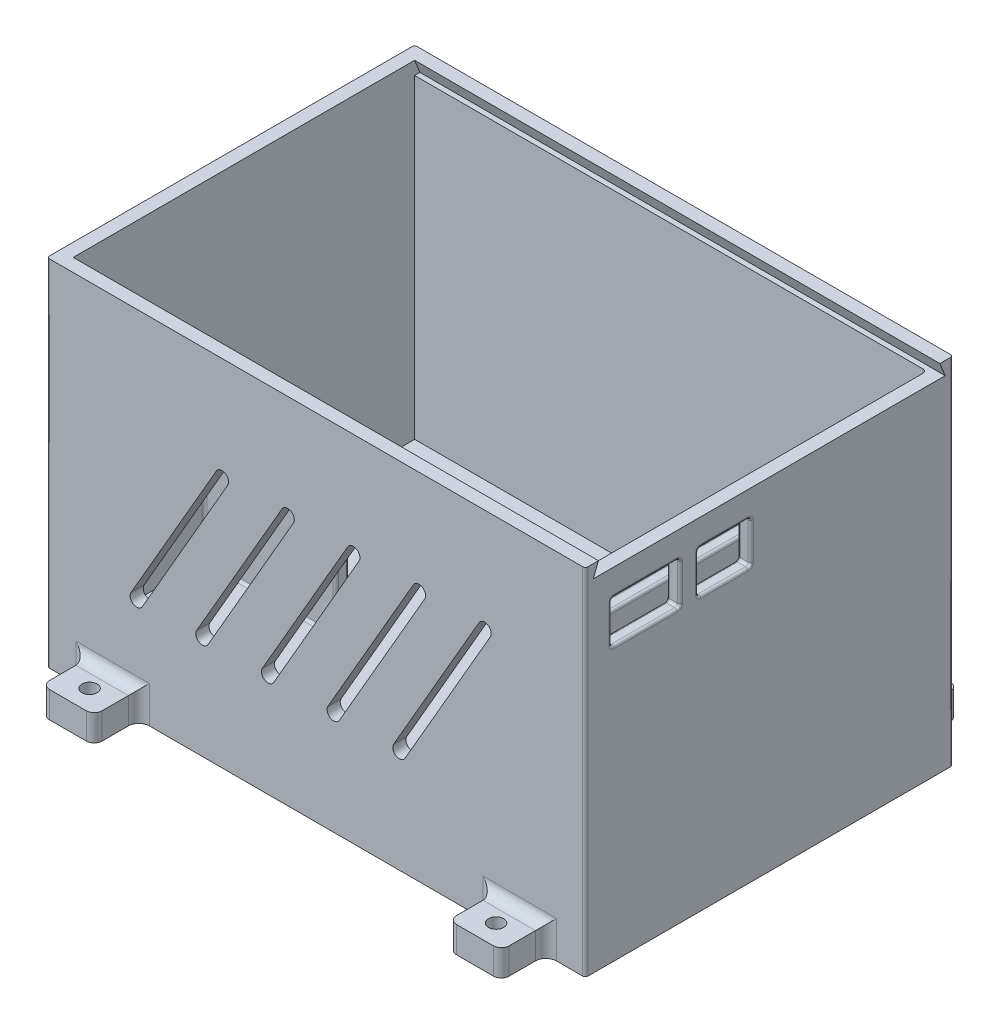
SolidWorks part; units mm, degrees
ref_plane "Front Plane" through (0, 0, 0) normal (0, 0, 1) x (1, 0, 0)
ref_plane "Top Plane" through (0, 0, 0) normal (0, 1, 0) x (1, 0, 0)
ref_plane "Right Plane" through (0, 0, 0) normal (1, 0, 0) x (0, 0, -1)
sketch "Sketch1" plane through (0, 0, 0) normal (0, 1, 0) x (1, 0, 0)
  line L1 (-90.8013, 98.9232) -> (114.1987, 98.9232)
  line L2 (-90.8013, 98.9232) -> (-90.8013, -41.0768)
  line L3 (-90.8013, -41.0768) -> (114.1987, -41.0768)
  line L4 (114.1987, 98.9232) -> (114.1987, -41.0768)
  dimension "D1" = 205
  dimension "D2" = 140
extrude "Boss-Extrude1" add sketch "Sketch1" along normal blind 130
sketch "Sketch2" plane through (0, 130, 0) normal (0, 1, 0) x (1, 0, 0)
  line L0 (114.1987, -41.0768) -> (114.1987, 98.9232) construction
  line L1 (-85.8013, 93.9232) -> (109.1987, 93.9232)
  line L2 (-85.8013, 93.9232) -> (-85.8013, -36.0768)
  line L3 (-85.8013, -36.0768) -> (109.1987, -36.0768)
  line L4 (109.1987, 93.9232) -> (109.1987, -36.0768)
  line L5 (-90.8013, 98.9232) -> (-90.8013, -41.0768) construction
  line L6 (114.1987, 98.9232) -> (-90.8013, 98.9232) construction
  line L7 (-90.8013, -41.0768) -> (114.1987, -41.0768) construction
  dimension "D2" = 5
  dimension "D3" = 5
  dimension "D1" = 5
  dimension "D4" = 5
extrude "Cut-Extrude1" cut sketch "Sketch2" against normal blind 120
sketch "Sketch3" plane through (0, 10, 0) normal (0, 1, 0) x (1, 0, 0)
  line L0 (59.1987, 93.9232) -> (59.1987, 18.9232)
  line L1 (109.1987, 93.9232) -> (-85.8013, 93.9232) construction
  line L2 (59.1987, 18.9232) -> (29.1987, 18.9232)
  line L3 (29.1987, 18.9232) -> (29.1987, 13.9232)
  line L4 (29.1987, 13.9232) -> (64.1987, 13.9232)
  line L5 (64.1987, 13.9232) -> (64.1987, 93.9232)
  line L6 (64.1987, 93.9232) -> (59.1987, 93.9232)
  line L7 (-85.8013, 18.9232) -> (-35.8013, 18.9232)
  line L8 (-85.8013, 93.9232) -> (-85.8013, -36.0768) construction
  line L9 (-35.8013, 18.9232) -> (-35.8013, 13.9232)
  line L10 (-35.8013, 13.9232) -> (-85.8013, 13.9232)
  line L11 (-85.8013, 13.9232) -> (-85.8013, 18.9232)
  dimension "D2" = 5
  dimension "D3" = 5
  dimension "D4" = 30
  dimension "D5" = 50
  dimension "D6" = 5
  dimension "D1" = 75
extrude "Boss-Extrude2" add sketch "Sketch3" along normal blind 56
sketch "Sketch4" plane through (0, 10, 0) normal (0, 1, 0) x (1, 0, 0)
  line L0 (109.1987, 6.9232) -> (91.1987, 6.9232)
  line L1 (109.1987, -36.0768) -> (109.1987, 93.9232) construction
  line L2 (91.1987, 6.9232) -> (91.1987, 3.9232)
  line L3 (91.1987, 3.9232) -> (109.1987, 3.9232)
  line L4 (109.1987, 3.9232) -> (109.1987, 6.9232)
  line L5 (109.1987, 93.9232) -> (64.1987, 93.9232) construction
  dimension "D1" = 3
  dimension "D2" = 87
  dimension "D3" = 18
extrude "Boss-Extrude3" add sketch "Sketch4" along normal blind 60
sketch "Sketch5" plane through (114.1987, 0, 0) normal (1, 0, 0) x (0, 0, -1)
  line L0 (-41.0768, 130) -> (98.9232, 130) construction
  line L1 (-31.0768, 120) -> (-5.0768, 120)
  line L2 (-31.0768, 120) -> (-31.0768, 104)
  line L3 (-31.0768, 104) -> (-5.0768, 104)
  line L4 (-5.0768, 120) -> (-5.0768, 104)
  line L5 (-41.0768, 130) -> (-41.0768, 0) construction
  dimension "D1" = 16
  dimension "D2" = 26
  dimension "D3" = 10
  dimension "D4" = 10
extrude "Cut-Extrude2" cut sketch "Sketch5" against normal blind 5
fillet "Fillet1" radius 1 4 edges at (111.6987, 104, 31.0768) (111.6987, 120, 31.0768) (111.6987, 120, 5.0768) (111.6987, 104, 5.0768)
fillet "Fillet2" radius 1 22 edges at (44.1987, 10, -18.9232) (29.1987, 10, -16.4232) (64.1987, 10, -53.9232) (-85.8013, 66, -16.4232) (-60.8013, 10, -18.9232) (29.1987, 38, -13.9232) (29.1987, 38, -18.9232) (46.6987, 10, -13.9232) (64.1987, 38, -13.9232) (64.1987, 66, -53.9232) (29.1987, 66, -16.4232) (46.6987, 66, -13.9232) (59.1987, 66, -56.4232) (44.1987, 66, -18.9232) (-60.8013, 66, -18.9232) (-60.8013, 66, -13.9232) (-85.8013, 38, -13.9232) (-85.8013, 38, -18.9232) (-35.8013, 38, -18.9232) (-35.8013, 38, -13.9232) (-60.8013, 10, -13.9232) (-35.8013, 10, -16.4232)
sketch "Sketch7" plane through (0, 130, 0) normal (0, 1, 0) x (1, 0, 0)
  line L0 (114.1987, 98.9232) -> (-90.8013, 98.9232)
  line L1 (-90.8013, 98.9232) -> (-90.8013, -41.0768)
  line L2 (-90.8013, -41.0768) -> (114.1987, -41.0768)
  line L3 (114.1987, -41.0768) -> (114.1987, 98.9232)
extrude "Boss-Extrude4" add sketch "Sketch7" along normal blind 5
sketch "Sketch9" plane through (0, 0, 41.0768) normal (0, 0, 1) x (1, 0, 0)
  line L0 (-26.2997, 96.7917) -> (-58.7997, 40.5)
  line L2 (-54.4696, 38) -> (-21.9696, 94.2917)
  line L4 (-90.8013, 30) -> (114.1987, 30) construction
  line L5 (-90.8013, 135) -> (-90.8013, 0) construction
  line L6 (114.1987, 135) -> (114.1987, 0) construction
  line L7 (-1.2997, 96.7917) -> (-33.7997, 40.5)
  line L9 (-29.4696, 38) -> (3.0304, 94.2917)
  line L10 (-90.8013, 0) -> (114.1987, 0) construction
  line L11 (23.7003, 96.7917) -> (-8.7997, 40.5)
  line L13 (-4.4696, 38) -> (28.0304, 94.2917)
  line L15 (48.7003, 96.7917) -> (16.2003, 40.5)
  line L17 (20.5304, 38) -> (53.0304, 94.2917)
  line L19 (73.7003, 96.7917) -> (41.2003, 40.5)
  line L21 (45.5304, 38) -> (78.0304, 94.2917)
  arc A0 (-26.2997, 96.7917) -> (-21.9696, 94.2917) centre (-24.1347, 95.5417) cw
  arc A1 (-54.4696, 38) -> (-58.7997, 40.5) centre (-56.6347, 39.25) cw
  arc A2 (-1.2997, 96.7917) -> (3.0304, 94.2917) centre (0.8653, 95.5417) cw
  arc A3 (-29.4696, 38) -> (-33.7997, 40.5) centre (-31.6347, 39.25) cw
  arc A4 (23.7003, 96.7917) -> (28.0304, 94.2917) centre (25.8653, 95.5417) cw
  arc A5 (-4.4696, 38) -> (-8.7997, 40.5) centre (-6.6347, 39.25) cw
  arc A6 (48.7003, 96.7917) -> (53.0304, 94.2917) centre (50.8653, 95.5417) cw
  arc A7 (20.5304, 38) -> (16.2003, 40.5) centre (18.3653, 39.25) cw
  arc A8 (73.7003, 96.7917) -> (78.0304, 94.2917) centre (75.8653, 95.5417) cw
  arc A9 (45.5304, 38) -> (41.2003, 40.5) centre (43.3653, 39.25) cw
  dimension "D6" = 5
  dimension "D4" = 5
  dimension "D22" = 2.5
  dimension "D23" = 2.5
  dimension "D24" = 2.5
  dimension "D25" = 2.5
  dimension "D26" = 2.5
  dimension "D27" = 2.5
  dimension "D28" = 2.5
  dimension "D29" = 2.5
  dimension "D30" = 2.5
  dimension "D31" = 2.5
  dimension "D1" = 60
  dimension "D2" = 8
  dimension "D3" = 65
  dimension "D5" = 65
  dimension "D7" = 65
  dimension "D8" = 5
  dimension "D9" = 65
  dimension "D10" = 5
  dimension "D11" = 65
  dimension "D13" = 8
  dimension "D14" = 8
  dimension "D15" = 8
  dimension "D16" = 8
  dimension "D17" = 25
  dimension "D18" = 25
  dimension "D19" = 25
  dimension "D20" = 25
  dimension "D21" = 65
  dimension "D12" = 5
  dimension "D32" = 5
  dimension "D33" = 5
  dimension "D34" = 5
  dimension "D35" = 5
  dimension "D36" = 34.1667
  dimension "D37" = 30
  dimension "D38" = 60
  dimension "D39" = 60
  dimension "D40" = 60
  dimension "D41" = 60
extrude "Cut-Extrude4" cut sketch "Sketch9" against normal blind 5
sketch "Sketch10" plane through (114.1987, 0, 0) normal (1, 0, 0) x (0, 0, -1)
  line L0 (98.9232, 135) -> (98.9232, 0) construction
  line L1 (-41.0768, 135) -> (98.9232, 135)
  line L2 (-41.0768, 135) -> (-41.0768, 130)
  line L3 (-41.0768, 130) -> (98.9232, 130)
  line L4 (98.9232, 135) -> (98.9232, 130)
  line L5 (-41.0768, 135) -> (-36.0768, 135)
  line L6 (-36.0768, 135) -> (-38.0768, 130)
  line L7 (-38.0768, 130) -> (-41.0768, 130)
  line L8 (98.9232, 135) -> (93.9232, 135)
  line L9 (93.9232, 135) -> (95.9232, 130)
  line L10 (95.9232, 130) -> (98.9232, 130)
  dimension "D3" = 5
  dimension "D4" = 5
  dimension "D2" = 3
extrude "Cut-Extrude5" cut sketch "Sketch10" against normal blind 200 contours L9 L1 L6 L3 region at (114.1987, 132.4874, -28.9232)
sketch "Sketch11" plane through (0, 0, 41.0768) normal (0, 0, 1) x (1, 0, 0)
  line L0 (-90.8013, 0) -> (114.1987, 0) construction
  line L1 (-75.8013, 10) -> (-55.8013, 10)
  line L2 (-75.8013, 10) -> (-75.8013, 0)
  line L3 (-75.8013, 0) -> (-55.8013, 0)
  line L4 (-55.8013, 10) -> (-55.8013, 0)
  line L5 (-90.8013, 135) -> (-90.8013, 0) construction
  line L6 (79.1987, 10) -> (99.1987, 10)
  line L7 (79.1987, 10) -> (79.1987, 0)
  line L8 (79.1987, 0) -> (99.1987, 0)
  line L9 (99.1987, 10) -> (99.1987, 0)
  line L10 (114.1987, 135) -> (114.1987, 0) construction
  dimension "D1" = 15
  dimension "D2" = 15
  dimension "D3" = 20
  dimension "D4" = 20
  dimension "D5" = 10
  dimension "D6" = 10
extrude "Boss-Extrude5" add sketch "Sketch11" along normal blind 17
sketch "Sketch12" plane through (0, 0, -98.9232) normal (0, 0, -1) x (-1, 0, 0)
  line L0 (-114.1987, 0) -> (90.8013, 0) construction
  line L1 (-99.1987, 10) -> (-79.1987, 10)
  line L2 (-99.1987, 10) -> (-99.1987, 0)
  line L3 (-99.1987, 0) -> (-79.1987, 0)
  line L4 (-79.1987, 10) -> (-79.1987, 0)
  line L5 (-114.1987, 135) -> (-114.1987, 0) construction
  line L6 (55.8013, 10) -> (75.8013, 10)
  line L7 (55.8013, 10) -> (55.8013, 0)
  line L8 (55.8013, 0) -> (75.8013, 0)
  line L9 (75.8013, 10) -> (75.8013, 0)
  line L10 (90.8013, 135) -> (90.8013, 0) construction
  dimension "D1" = 15
  dimension "D2" = 15
  dimension "D3" = 20
  dimension "D4" = 20
  dimension "D5" = 10
  dimension "D6" = 10
extrude "Boss-Extrude6" add sketch "Sketch12" along normal blind 17
sketch "Sketch13" plane through (0, 10, 0) normal (0, 1, 0) x (1, 0, 0)
  line L0 (-75.8013, 115.9232) -> (-75.8013, 98.9232) construction
  line L1 (79.1987, 115.9232) -> (79.1987, 98.9232) construction
  line L2 (79.1987, -58.0768) -> (79.1987, -41.0768) construction
  line L3 (79.1987, 115.9232) -> (99.1987, 115.9232) construction
  line L4 (-75.8013, 115.9232) -> (-55.8013, 115.9232) construction
  line L5 (-55.8013, -58.0768) -> (-75.8013, -58.0768) construction
  line L6 (99.1987, -58.0768) -> (79.1987, -58.0768) construction
  circle A0 centre (-65.8013, 107.9232) radius 2.9
  circle A1 centre (89.1987, 107.9232) radius 2.9
  circle A2 centre (89.1987, -50.0768) radius 2.9
  circle A3 centre (-65.5796, -50.0768) radius 2.9
  dimension "D1" = 5.8
  dimension "D2" = 5.8
  dimension "D3" = 5.8
  dimension "D4" = 5.8
  dimension "D5" = 10
  dimension "D6" = 10
  dimension "D7" = 10
  dimension "D8" = 8
  dimension "D9" = 8
  dimension "D10" = 8
  dimension "D11" = 8
extrude "Cut-Extrude6" cut sketch "Sketch13" against normal blind 17
fillet "Fillet5" radius 4 6 edges at (-55.8013, 5, -98.9232) (99.1987, 5, -98.9232) (79.1987, 5, -98.9232) (-75.8013, 5, -98.9232) (-65.8013, 10, -98.9232) (89.1987, 10, -98.9232)
fillet "Fillet6" radius 4 6 edges at (-55.8013, 5, 41.0768) (99.1987, 5, 41.0768) (89.1987, 10, 41.0768) (79.1987, 5, 41.0768) (-65.8013, 10, 41.0768) (-75.8013, 5, 41.0768)
fillet "Fillet10" radius 3 8 edges at (-75.8013, 5, 58.0768) (-55.8013, 5, 58.0768) (99.1987, 5, 58.0768) (79.1987, 5, 58.0768) (99.1987, 5, -115.9232) (79.1987, 5, -115.9232) (-75.8013, 5, -115.9232) (-55.8013, 5, -115.9232)
sketch "Sketch14" plane through (0, 0, -6.9232) normal (0, 0, -1) x (-1, 0, 0)
  line L0 (-109.1987, 10) -> (-91.1987, 10) construction
  line L1 (-91.1987, 70) -> (-94.1987, 70)
  line L2 (-91.1987, 70) -> (-91.1987, 10)
  line L3 (-91.1987, 10) -> (-94.1987, 10)
  line L4 (-94.1987, 70) -> (-94.1987, 10)
  dimension "D1" = 3
extrude "Boss-Extrude7" add sketch "Sketch14" along normal blind 7
sketch "Sketch16" plane through (0, 0, -93.9232) normal (0, 0, 1) x (1, 0, 0)
  line L0 (109.1987, 10) -> (65.1987, 10) construction
  line L1 (103.1987, 10) -> (100.1987, 10)
  line L2 (103.1987, 10) -> (103.1987, 70)
  line L3 (103.1987, 70) -> (100.1987, 70)
  line L4 (100.1987, 10) -> (100.1987, 70)
  line L5 (109.1987, 10) -> (109.1987, 130) construction
  dimension "D1" = 3
  dimension "D2" = 60
  dimension "D3" = 6
extrude "Boss-Extrude8" add sketch "Sketch16" along normal blind 7
fillet "Fillet11" radius 1.5 29 edges at (59.1987, 37.5, -93.9232) (59.4916, 65.7071, -93.9232) (61.6987, 66, -93.9232) (63.9058, 65.7071, -93.9232) (82.6987, 10, -93.9232) (64.4916, 10.2929, -93.9232) (-85.8013, 70, 36.0768) (109.1987, 70, 36.0768) (11.6987, 10, 36.0768) (100.1987, 10, -3.9232) (109.1987, 10, 16.0768) (94.1987, 40, -6.9232) (109.1987, 40, -3.9232) (109.1987, 40, -6.9232) (101.6987, 10, -6.9232) (109.1987, 10, -50.4232) (109.1987, 70, -93.9232) (106.1987, 10, -93.9232) (101.6987, 70, -93.9232) (103.1987, 10, -90.4232) (103.1987, 40, -93.9232) (101.6987, 10, -86.9232) (100.1987, 10, -90.4232) (64.1987, 38, -93.9232) (100.1987, 40, -93.9232) (91.1987, 40, -3.9232) (91.1987, 10, -8.9232) (92.6987, 10, -13.9232) (94.1987, 10, -10.4232)
sketch "Sketch18" plane through (114.1987, 0, 0) normal (1, 0, 0) x (0, 0, -1)
  line L0 (-5.0768, 105) -> (-5.0768, 119) construction
  line L1 (1.9232, 120) -> (21.9232, 120)
  line L2 (1.9232, 120) -> (1.9232, 104.0299)
  line L3 (1.9232, 104.0299) -> (21.9232, 104.0299)
  line L4 (21.9232, 120) -> (21.9232, 104.0299)
  line L5 (-6.0768, 120) -> (-30.0768, 120) construction
  dimension "D1" = 7
  dimension "D2" = 20
  dimension "D3" = 0
extrude "Cut-Extrude7" cut sketch "Sketch18" against normal blind 5
fillet "Fillet12" radius 1 28 edges at (109.1987, 120, -11.9232) (114.1987, 120, -11.9232) (109.1987, 112.015, -1.9232) (109.1987, 112.015, -21.9232) (114.1987, 112.015, -1.9232) (114.1987, 112.015, -21.9232) (114.1987, 104.2929, 30.7839) (114.1987, 112, 31.0768) (114.1987, 119.7071, 30.7839) (114.1987, 120, 18.0768) (114.1987, 119.7071, 5.3697) (114.1987, 112, 5.0768) (114.1987, 104.2929, 5.3697) (109.1987, 104.2929, 30.7839) (109.1987, 112, 31.0768) (109.1987, 119.7071, 30.7839) (109.1987, 120, 18.0768) (109.1987, 119.7071, 5.3697) (109.1987, 112, 5.0768) (109.1987, 104.2929, 5.3697) (114.1987, 104, 18.0768) (109.1987, 104, 18.0768) (109.1987, 104.0299, -11.9232) (114.1987, 104.0299, -11.9232) (111.6987, 120, -21.9232) (111.6987, 104.0299, -21.9232) (111.6987, 120, -1.9232) (111.6987, 104.0299, -1.9232)
fillet "Fillet14" radius 1 4 edges at (114.1987, 67.5, 41.0768) (114.1987, 67.5, -98.9232) (-90.8013, 67.5, -98.9232) (-90.8013, 67.5, 41.0768)
equation "\"Module Height\"= 12cm"
equation "\"Module Length\"= 150mm"
equation "\"Module Width\"= 75mm"
equation "\"Wall thickness\"= 5mm"
equation "\"Encasing Width\"= \"Module Width\" + \"Wall thickness\" * 3 + 50"
equation "\"Encasing length\"= \"Module Length\" + \"Wall thickness\" * 3 + 40mm"
equation "\"Support wall height\"= \"Module Height\" * 7 / 15"
equation "\"Support wall 1 lenght\"= \"Module Length\" * 1 / 3"
equation "\"support wall 2 length\"= \"Module Length\" / 5"
equation "\"Encasing height no lid\"= \"Module Height\" + 10mm"
equation "\"D5@Sketch3\"=\"Support wall 1 lenght\""
equation "\"D4@Sketch3\"=\"support wall 2 length\""
equation "\"D2@Sketch3\"=\"Wall thickness\""
equation "\"D6@Sketch3\"=\"Wall thickness\""
equation "\"D1@Sketch3\"=\"Module Width\""
equation "\"D3@Sketch3\"=\"Wall thickness\""
equation "\"D1@Boss-Extrude2\"=\"Support wall height\""
equation "\"D2@Sketch2\"=\"Wall thickness\""
equation "\"D3@Sketch2\"=\"Wall thickness\""
equation "\"D4@Sketch2\"=\"Wall thickness\""
equation "\"D1@Sketch2\"=\"Wall thickness\""
equation "\"D1@Cut-Extrude1\"=\"Module Height\""
equation "\"D2@Sketch1\"=\"Encasing Width\""
equation "\"D1@Sketch1\"=\"Encasing length\""
equation "\"D1@Boss-Extrude1\"=\"Encasing height no lid\""
equation "\"D1@Cut-Extrude2\"=\"Wall thickness\""
equation "\"Lid lenght\"= \"Encasing length\" - \"Wall thickness\""
equation "\"D1@Cut-Extrude4\"= \"Wall thickness\""
equation "\"D4@Sketch10\"=\"Wall thickness\""
equation "\"D3@Sketch10\"=\"Wall thickness\""
equation "\"D1@Cut-Extrude5\"=\"Lid lenght\""
equation "\"Microcontroller Length\"= 84mm"
equation "\"Microcontroller width\"= 52mm"
equation "\"D36@Sketch9\"=\"Encasing length\"/6"
equation "\"D1@Cut-Extrude7\"=\"Wall thickness\""
